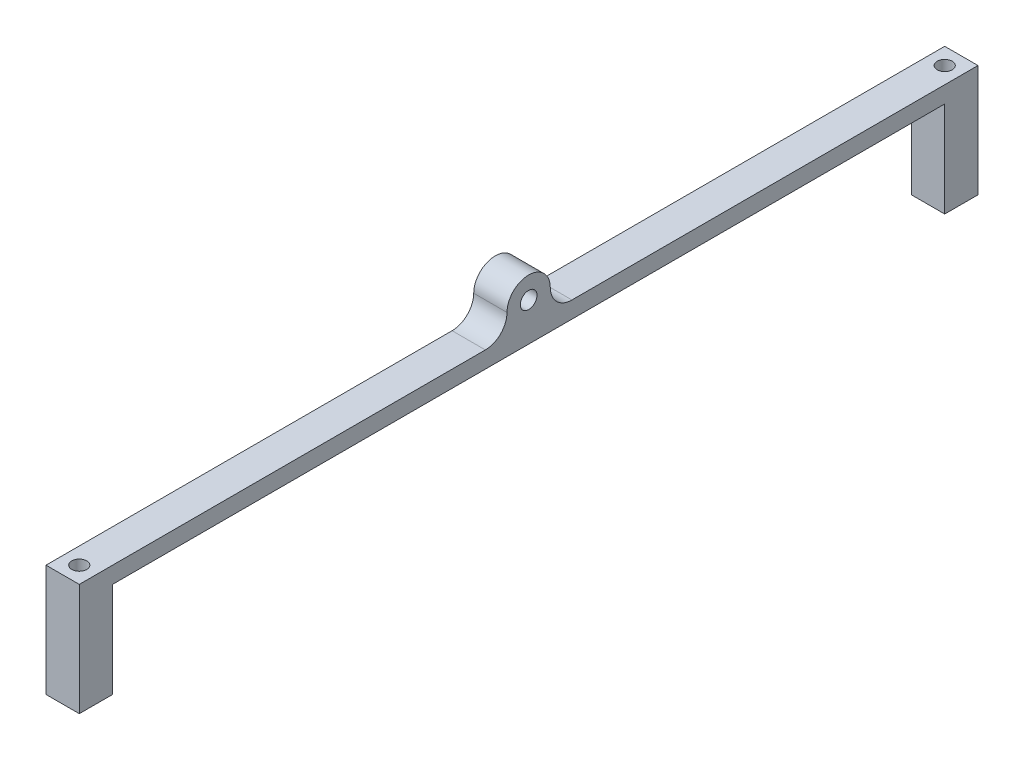
SolidWorks part; units mm, degrees
ref_plane "Спереди" through (0, 0, 0) normal (0, 0, 1) x (1, 0, 0)
ref_plane "Сверху" through (0, 0, 0) normal (0, 1, 0) x (1, 0, 0)
ref_plane "Справа" through (0, 0, 0) normal (1, 0, 0) x (0, 0, -1)
other "Configuration Table"
sketch "Эскиз1" plane through (0, 0, 0) normal (0, 1, 0) x (1, 0, 0)
  line L1 (0, 270) -> (10, 270)
  line L2 (0, 270) -> (0, 0)
  line L3 (0, 0) -> (10, 0)
  line L4 (10, 270) -> (10, 0)
  line L5 (342.3, 270) -> (342.3, 0) construction
  line L7 (0, 260) -> (10, 270) construction
  line L10 (0, 260) -> (10, 260) construction
  line L14 (0, 10) -> (10, 10) construction
  line L16 (0, 270) -> (10, 260) construction
  line L17 (0, 10) -> (10, 0) construction
  line L18 (10, 10) -> (0, 0) construction
  circle A0 centre (5, 265) radius 2.25
  circle A1 centre (5, 5) radius 2.25
  dimension "D5" = 4.5
  dimension "D6" = 4.5
  dimension "D2" = 10
  dimension "D3" = 10
  dimension "D4" = 10
extrude "Бобышка-Вытянуть1" add sketch "Эскиз1" along normal blind 5
sketch "Эскиз2" plane through (0, 0, 0) normal (1, 0, 0) x (0, 0, -1)
  line L0 (128.5, 11.5) -> (141.5, 11.5) construction
  line L1 (122, 5) -> (148, 5)
  line L2 (0, 5) -> (270, 5) construction
  arc A0 (141.5, 11.5) -> (128.5, 11.5) centre (135, 11.5) ccw
  arc A2 (122, 5) -> (128.5, 11.5) centre (122, 11.5) ccw
  arc A3 (141.5, 11.5) -> (148, 5) centre (148, 11.5) ccw
  circle A4 centre (135, 11.5) radius 2.5
  point P1 (135, 5)
  point P5 (135, 5)
  point P6 (141.5, 11.5)
  point P7 (128.5, 11.5)
  dimension "D1" = 13
  dimension "D2" = 13
  dimension "D3" = 13
  dimension "D4" = 5
extrude "Бобышка-Вытянуть2" add sketch "Эскиз2" along normal blind 10
sketch "Эскиз3" plane through (0, 0, 0) normal (0, -1, 0) x (1, 0, 0)
  line L0 (10, 0) -> (10, -270) construction
  line L1 (0, 0) -> (10, 0)
  line L2 (0, 0) -> (0, -10)
  line L3 (0, -10) -> (10, -10)
  line L4 (10, 0) -> (10, -10)
  line L6 (0, -270) -> (10, -270)
  line L7 (0, -270) -> (0, -260)
  line L8 (0, -260) -> (10, -260)
  line L9 (10, -270) -> (10, -260)
  circle A526 centre (5, -265) radius 2.25
  circle A527 centre (5, -265) radius 2.25
  circle A529 centre (5, -5) radius 2.25
  circle A530 centre (5, -5) radius 2.25
  dimension "D1" = 10
  dimension "D2" = 10
  dimension "D3" = 0
  dimension "D4" = 0
extrude "Бобышка-Вытянуть3" add sketch "Эскиз3" along normal up to surface (28.65 mm away)
